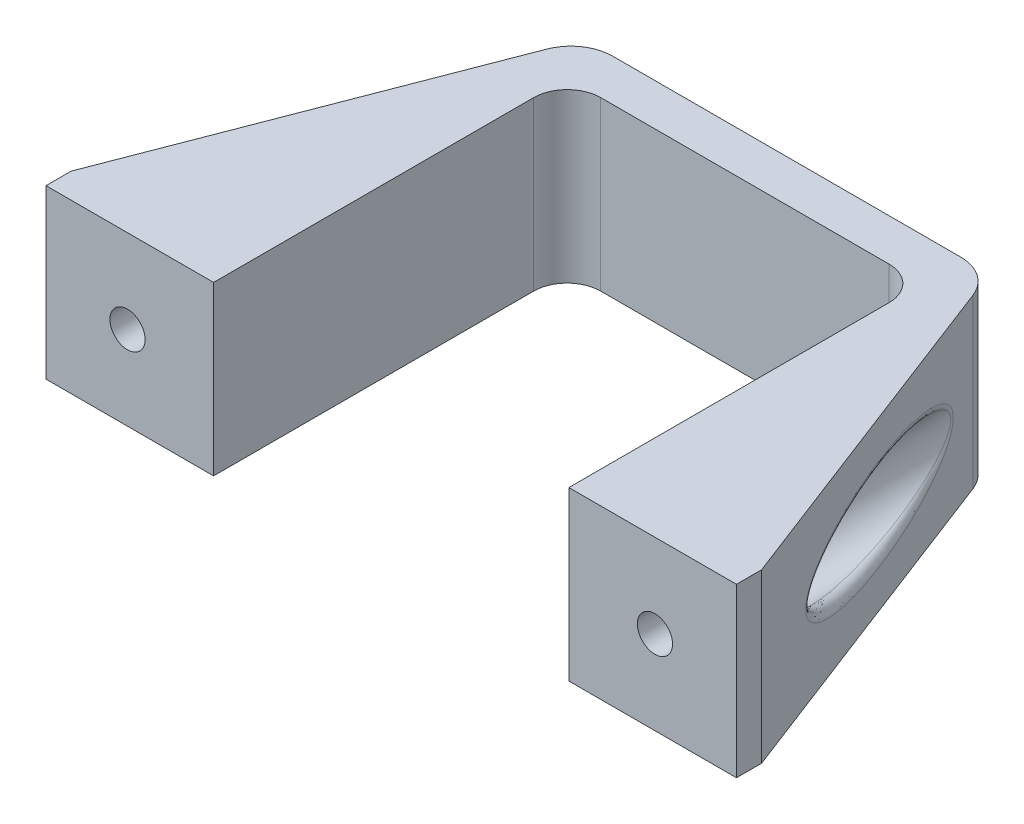
SolidWorks part; units mm, degrees
ref_plane "前视基准面" through (0, 0, 0) normal (0, 0, 1) x (1, 0, 0)
ref_plane "上视基准面" through (0, 0, 0) normal (0, 1, 0) x (1, 0, 0)
ref_plane "右视基准面" through (0, 0, 0) normal (1, 0, 0) x (0, 0, -1)
other "Configuration Table"
sketch "草图1" plane through (0, 0, 0) normal (0, 1, 0) x (1, 0, 0)
  line L0 (-21.2, 6.0133) -> (-21.2, 0)
  line L1 (-21.2, 42.2) -> (21.2, 42.2)
  line L2 (21.2, 42.2) -> (21.2, 6.0133)
  line L4 (41.2, 3) -> (41.2, 0)
  line L5 (41.2, 0) -> (21.2, 0)
  line L7 (0, 42.2) -> (0, 47.2)
  line L8 (-24.2, 47.2) -> (24.2, 47.2)
  line L10 (21.2, 6.0133) -> (21.2, 0)
  line L12 (-41.2, 0) -> (-21.2, 0)
  line L13 (-41.2, 3) -> (-41.2, 0)
  line L15 (-21.2, 42.2) -> (-21.2, 6.0133)
  line L16 (-24.2, 47.2) -> (-41.2, 3)
  line L17 (24.2, 47.2) -> (41.2, 3)
  dimension "D1" = 21.2
  dimension "D2" = 42.2
  dimension "D3" = 20
  dimension "D4" = 3
  dimension "D5" = 5
extrude "凸台-拉伸1" add sketch "草图1" along normal blind 20 contours L8 L17 L4 L5 L10 L2 L1 L15 L0 L12 L13 L16
fillet "圆角1" radius 5 2 edges at (-24.2, 10, -47.2) (24.2, 10, -47.2)
fillet "圆角2" radius 4 2 edges at (-21.2, 10, -42.2) (21.2, 10, -42.2)
sketch "草图2" plane through (0, 0, 0) normal (0, 0, 1) x (1, 0, 0)
  line L0 (0, 0) -> (0, 20) construction
  line L1 (-17.2, 20) -> (17.2, 20) construction
  circle A0 centre (-31.4723, 10) radius 2.1
  circle A1 centre (31.4723, 10) radius 2.1
  dimension "D1" = 4.2
extrude "切除-拉伸1" cut sketch "草图2" against normal blind 57
sketch "草图3" plane through (0, 0, -47.2) normal (0, 0, -1) x (-1, 0, 0)
  circle A0 centre (31.4723, 10) radius 4
  circle A1 centre (-31.4723, 10) radius 4.5
  dimension "D1" = 9
  dimension "D2" = 8
extrude "切除-拉伸2" cut sketch "草图3" against normal blind 44
fillet "圆角4" radius 1 2 edges at (-27.4723, 10, -38.6919) (26.9723, 10, -39.9919)
